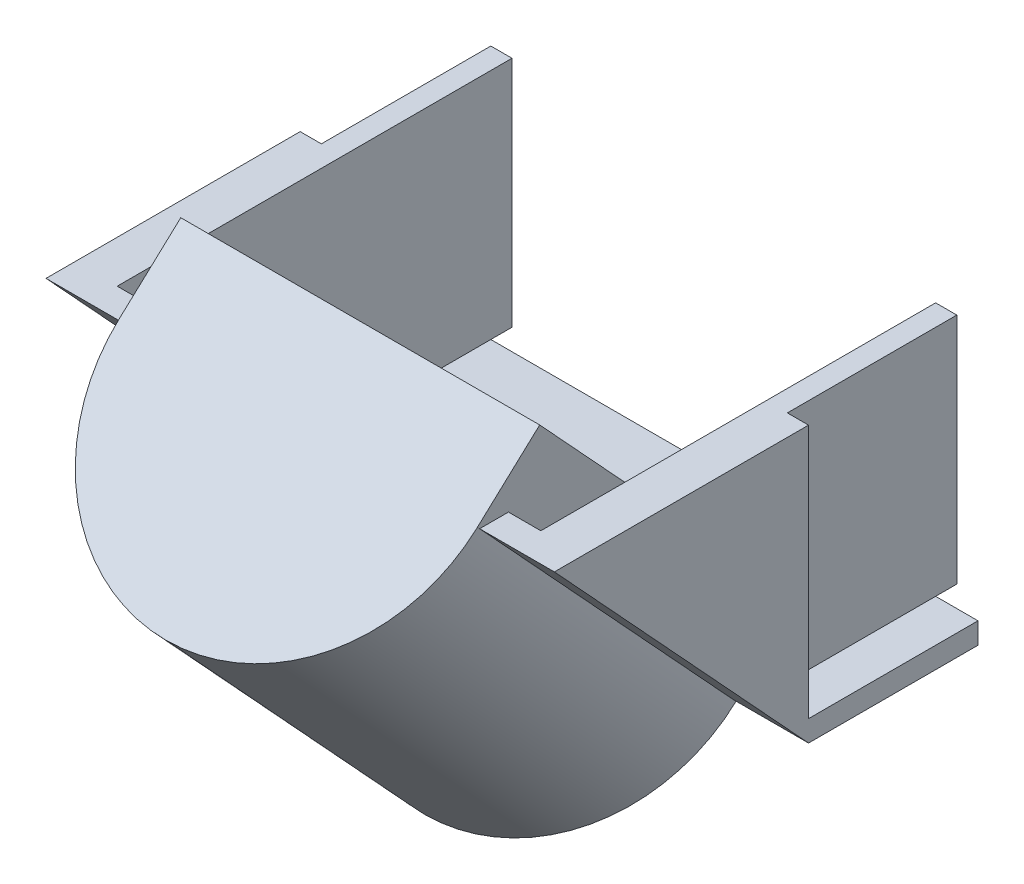
SolidWorks part; units mm, degrees
ref_plane "Front Plane" through (0, 0, 0) normal (0, 0, 1) x (1, 0, 0)
ref_plane "Top Plane" through (0, 0, 0) normal (0, 1, 0) x (1, 0, 0)
ref_plane "Right Plane" through (0, 0, 0) normal (1, 0, 0) x (0, 0, -1)
sketch "Sketch4" plane through (0, 0, 0) normal (1, 0, 0) x (0, 0, -1)
  line L0 (0, 0) -> (0, 82.55)
  line L5 (0, 82.55) -> (-76.2, 82.55)
  line L6 (-76.2, 82.55) -> (0, 0)
  line L21 (0, 0) -> (0, 6.35)
  line L25 (0, 76.2) -> (0, 12.7)
  dimension "D1" = 82.55
  dimension "D2" = 76.2
extrude "Boss-Extrude2" add sketch "Sketch4" along normal blind 76.2 and the other way blind 76.2 contours L6 L0 L5
sketch "Sketch6" plane through (0, 0, 0) normal (0, 0, -1) x (-1, 0, 0)
  line L0 (76.2, 0) -> (76.2, 82.55) construction
  line L1 (-76.2, 0) -> (76.2, 0)
  line L2 (-76.2, 0) -> (-76.2, 6.35)
  line L3 (-76.2, 6.35) -> (76.2, 6.35)
  line L4 (76.2, 0) -> (76.2, 6.35)
  line L5 (76.2, 82.55) -> (-76.2, 82.55) construction
  line L6 (-69.85, 82.55) -> (-63.5, 82.55)
  line L7 (-69.85, 82.55) -> (-69.85, 12.7)
  line L8 (-69.85, 12.7) -> (-63.5, 12.7)
  line L9 (-63.5, 82.55) -> (-63.5, 12.7)
  line L10 (0, 0) -> (0, 82.55) construction
  line L11 (69.85, 12.7) -> (63.5, 12.7)
  line L12 (63.5, 82.55) -> (63.5, 12.7)
  line L13 (69.85, 82.55) -> (63.5, 82.55)
  line L14 (69.85, 82.55) -> (69.85, 12.7)
  dimension "D1" = 6.35
  dimension "D2" = 139.7
  dimension "D3" = 6.35
  dimension "D4" = 6.35
extrude "Boss-Extrude3" add sketch "Sketch6" along normal blind 50.8
sketch "Sketch7" plane through (0, 0, 0) normal (0, 0, -1) x (-1, 0, 0)
  line L1 (-63.5, 82.55) -> (63.5, 82.55)
  line L2 (-63.5, 82.55) -> (-63.5, 12.7)
  line L3 (-63.5, 12.7) -> (63.5, 12.7)
  line L4 (63.5, 82.55) -> (63.5, 12.7)
extrude "Cut-Extrude3" cut sketch "Sketch7" against normal offset from surface (67.5582 mm away) 6.35 up to face at (0, 41.275, 38.1)
ref_plane "Plane1" through (0, 41.275, 38.1) normal (0, -0.7348, -0.6783) x (-1, 0, 0)
sketch "Sketch8" plane through (0, 41.275, 38.1) normal (0, -0.7348, -0.6783) x (-1, 0, 0)
  line L0 (-53.7989, 0) -> (-53.7989, 25.4)
  line L5 (-53.7989, 25.4) -> (53.7989, 25.4)
  line L6 (32.0909, -32.0909) -> (45.3833, -45.3833) construction
  line L7 (53.7989, 25.4) -> (53.7989, 0)
  arc A2 (-53.7989, 0) -> (53.7989, 0) centre (0, 0) ccw
  point P0 (0, 0)
  dimension "D1" = 25.4
extrude "Boss-Extrude5" add sketch "Sketch8" along normal mid plane 114.3 contours L5 L7 A2 L0
equation "\"t\"= .005in"
